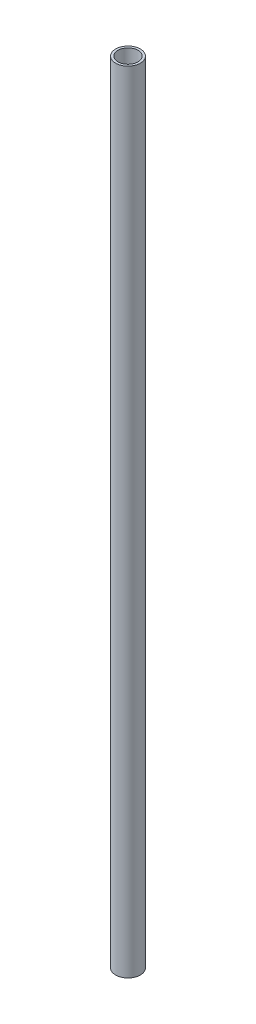
SolidWorks part; units mm, degrees
material "AISI 4130 Steel, annealed at 865C"
ref_plane "Front Plane" through (0, 0, 0) normal (0, 0, 1) x (1, 0, 0)
ref_plane "Top Plane" through (0, 0, 0) normal (0, 1, 0) x (1, 0, 0)
ref_plane "Right Plane" through (0, 0, 0) normal (1, 0, 0) x (0, 0, -1)
sketch "Sketch1" plane through (0, 0, 0) normal (0, 1, 0) x (1, 0, 0)
  circle A0 centre (0, 0) radius 6.4643
  circle A1 centre (0, 0) radius 7.9375
  dimension "D1" = 15.875
  dimension "D2" = 12.9286
extrude "Boss-Extrude1" add sketch "Sketch1" along normal blind 508
ref_axis "Axis1" through (0, 508, 0) along (0, -1, 0)
